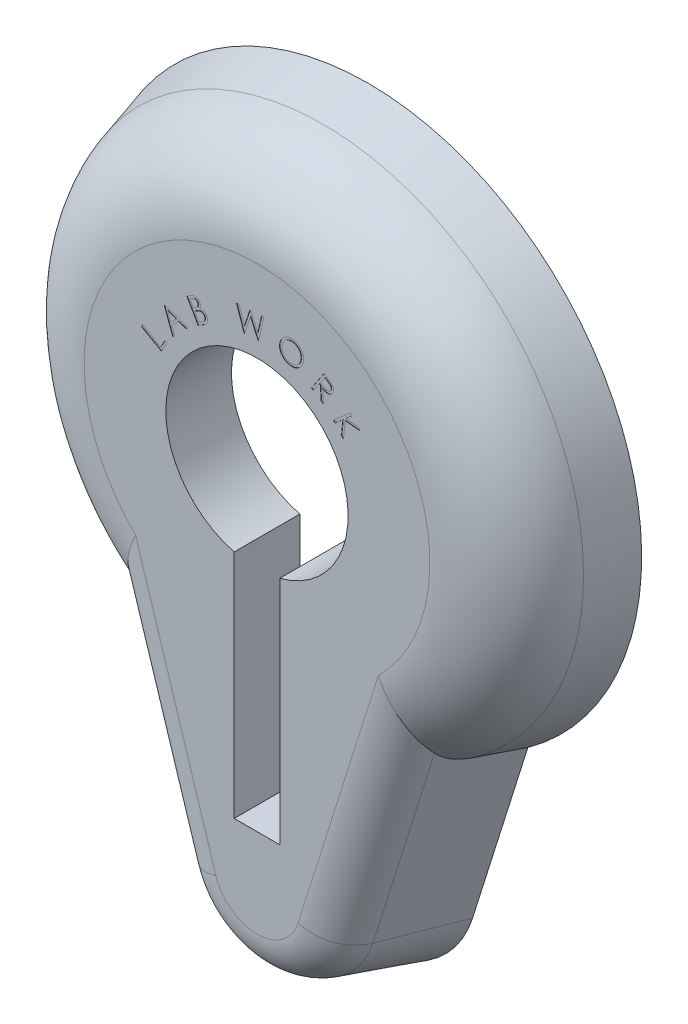
SolidWorks part; units mm, degrees
material "Brass"
ref_plane "Front Plane" through (0, 0, 0) normal (0, 0, 1) x (1, 0, 0)
ref_plane "Top Plane" through (0, 0, 0) normal (0, 1, 0) x (1, 0, 0)
ref_plane "Right Plane" through (0, 0, 0) normal (1, 0, 0) x (0, 0, -1)
sketch "Sketch1" plane through (0, 0, 0) normal (0, 0, 1) x (1, 0, 0)
  line L0 (0, 0) -> (0, 69.987) construction
  line L1 (-14.5346, -4.5828) -> (-22.2438, 19.8674)
  line L2 (14.5346, -4.5828) -> (22.2438, 19.8674)
  arc A0 (-14.5346, -4.5828) -> (14.5346, -4.5828) centre (0, 0) ccw
  arc A1 (-22.2438, 19.8674) -> (22.2438, 19.8674) centre (0, 50.8) cw
  point P9 (0, -0.959)
  dimension "D1" = 15.24
  dimension "D2" = 38.1
  dimension "D3" = 50.8
  dimension "D4" = 35
extrude "Boss-Extrude2" add sketch "Sketch1" along normal blind 15.494 draft 16
fillet "Fillet1" radius 6.35 3 edges at (14.3818, 9.7071, 15.494) (0, -10.7972, 15.494) (-14.3818, 9.7071, 15.494)
fillet "Fillet2" radius 12.7 1 edges at (0, 84.4572, 15.494)
sketch "Sketch2" plane through (0, 0, 0) normal (0, 0, -1) x (-1, 0, 0)
  line L4 (12.1122, -3.819) -> (20.0801, 21.4521)
  line L5 (-20.0801, 21.4521) -> (-12.1122, -3.819)
  line L6 (12.1122, -3.819) -> (20.0801, 21.4521)
  line L7 (-20.0801, 21.4521) -> (-12.1122, -3.819)
  arc A4 (-12.1122, -3.819) -> (12.1122, -3.819) centre (0, 0) ccw
  arc A5 (20.0801, 21.4521) -> (-20.0801, 21.4521) centre (0, 50.8) ccw
  arc A6 (-12.1122, -3.819) -> (12.1122, -3.819) centre (0, 0) ccw
  arc A7 (20.0801, 21.4521) -> (-20.0801, 21.4521) centre (0, 50.8) ccw
  dimension "D1" = 2.54
extrude "Cut-Extrude1" cut sketch "Sketch2" against normal blind 6.35 draft 16
sketch "Sketch3" plane through (0, 0, 15.494) normal (0, 0, 1) x (1, 0, 0)
  circle A0 centre (0, 50.8) radius 12.7
  dimension "D1" = 25.4
extrude "Cut-Extrude2" cut sketch "Sketch3" against normal through all
sketch "Sketch4" plane through (0, 0, 15.494) normal (0, 0, 1) x (1, 0, 0)
  line L0 (0, 6.35) -> (0, 0) construction
  line L1 (-3.175, 57.15) -> (3.175, 57.15)
  line L2 (-3.175, 57.15) -> (-3.175, 6.35)
  line L3 (-3.175, 6.35) -> (3.175, 6.35)
  line L4 (3.175, 57.15) -> (3.175, 6.35)
  point P6 (0, 0)
  dimension "D1" = 6.35
  dimension "D2" = 50.8
  dimension "D3" = 6.35
extrude "Cut-Extrude3" cut sketch "Sketch4" against normal through all contours L2 L1 L4 L3
sketch "Sketch5" plane through (0, 0, 15.494) normal (0, 0, 1) x (1, 0, 0)
  arc A0 (-13.511, 57.3352) -> (13.356, 57.6464) centre (0, 50.8) cw construction
  text T0 "LAB WORK "
extrude "Cut-Extrude4" cut sketch "Sketch5" against normal blind 0.0508
